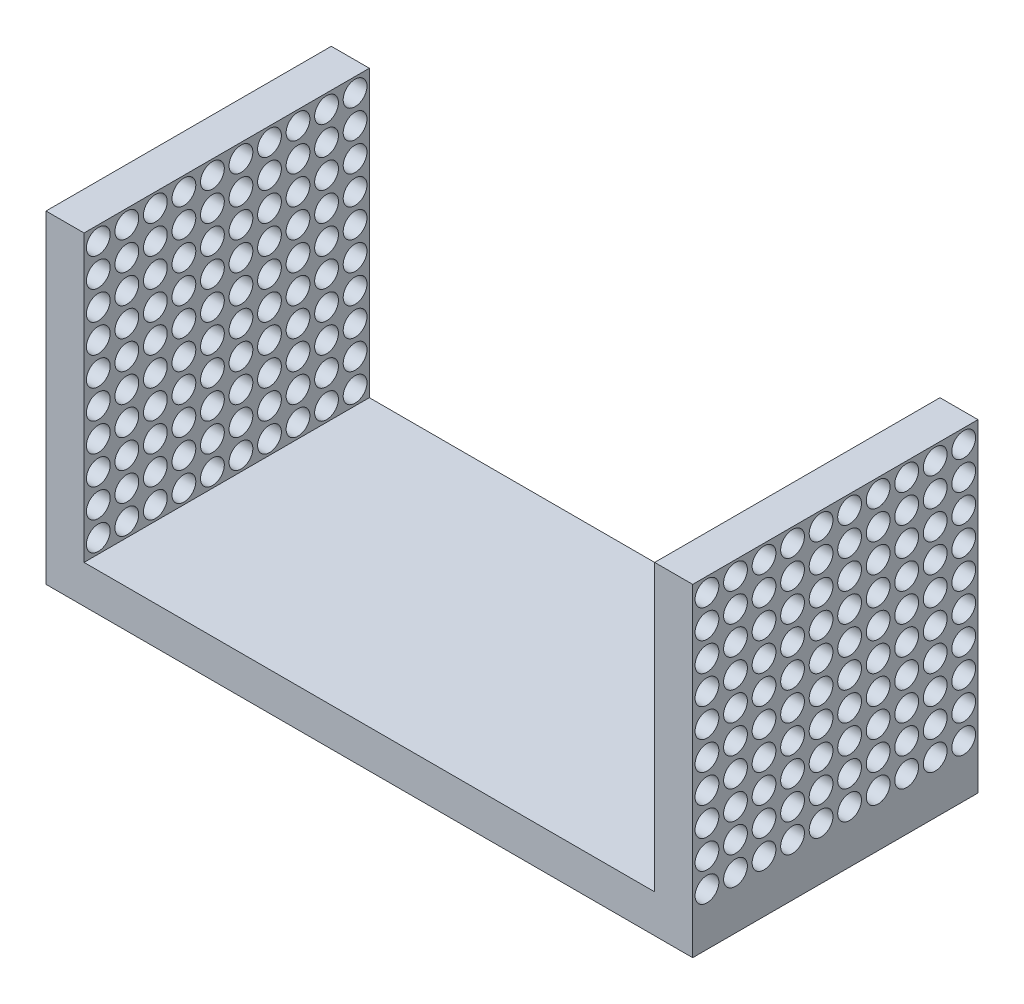
SolidWorks part; units mm, degrees
ref_plane "Front Plane" through (0, 0, 0) normal (0, 0, 1) x (1, 0, 0)
ref_plane "Top Plane" through (0, 0, 0) normal (0, 1, 0) x (1, 0, 0)
ref_plane "Right Plane" through (0, 0, 0) normal (1, 0, 0) x (0, 0, -1)
sketch "Sketch1" plane through (0, 0, 0) normal (0, 0, 1) x (1, 0, 0)
  line L1 (17, -8.5) -> (-17, -8.5)
  line L2 (17, -8.5) -> (17, 8.5)
  line L3 (17, 8.5) -> (-17, 8.5)
  line L4 (-17, -8.5) -> (-17, 8.5)
  line L5 (17, -8.5) -> (-17, 8.5) construction
  line L6 (17, 8.5) -> (-17, -8.5) construction
  point P0 (0, 0)
  dimension "D1" = 34
  dimension "D2" = 17
extrude "Boss-Extrude1" add sketch "Sketch1" along normal blind 7.5 and the other way blind 7.5
sketch "Sketch2" plane through (0, 0, 7.5) normal (0, 0, 1) x (1, 0, 0)
  line L0 (17, 8.5) -> (-17, 8.5) construction
  line L1 (15, -6.5) -> (-15, -6.5)
  line L2 (15, -6.5) -> (15, 8.5)
  line L3 (15, 8.5) -> (-15, 8.5)
  line L4 (-15, -6.5) -> (-15, 8.5)
  line L5 (15, -6.5) -> (-15, 8.5) construction
  line L6 (15, 8.5) -> (-15, -6.5) construction
  line L7 (-17, -8.5) -> (17, -8.5) construction
  line L8 (-17, 8.5) -> (-17, -8.5) construction
  line L9 (0, 1) -> (0, 0) construction
  point P0 (0, 1)
  dimension "D1" = 2
  dimension "D2" = 2
extrude "Cut-Extrude1" cut sketch "Sketch2" against normal up to surface (15 mm away) up to face at (0, 0, -7.5)
sketch "Sketch3" plane through (17, 0, 0) normal (1, 0, 0) x (0, 0, -1)
  line L0 (-6.75, 7.75) -> (-6.75, 8.5) construction
  line L1 (7.5, 8.5) -> (-7.5, 8.5) construction
  line L2 (-6.75, 7.75) -> (-7.5, 7.75) construction
  line L3 (-7.5, -8.5) -> (-7.5, 8.5) construction
  circle A0 centre (-6.75, 7.75) radius 0.625
  dimension "D3" = 1.25
  dimension "D1" = 0.75
  dimension "D2" = 0.75
extrude "Cut-Extrude2" cut sketch "Sketch3" against normal up to surface (34 mm away) up to face at (-17, 0, 0)
pattern_linear "LPattern1" count 10 spacing 1.5 along (0, 0, -1) count 10 spacing 1.5 along (0, -1, 0) of "Cut-Extrude2"
